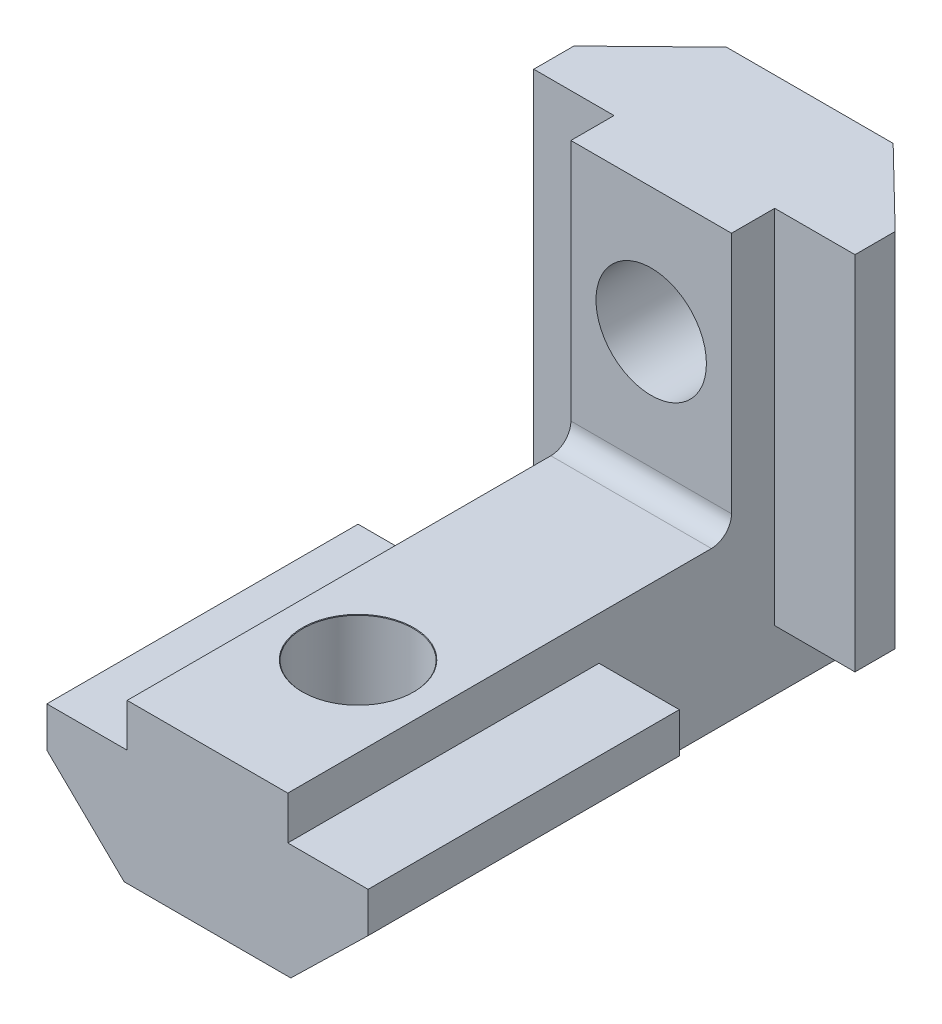
SolidWorks part; units mm, degrees
ref_plane "Piano frontale" through (0, 0, 0) normal (0, 0, 1) x (1, 0, 0)
ref_plane "Piano superiore" through (0, 0, 0) normal (0, 1, 0) x (1, 0, 0)
ref_plane "Piano destro" through (0, 0, 0) normal (1, 0, 0) x (0, 0, -1)
sketch "Schizzo1" plane through (0, 0, 0) normal (0, 0, 1) x (1, 0, 0)
  line L0 (-4.15, 0) -> (4.15, 0)
  line L1 (-4.15, 0) -> (-8, 3.75)
  line L2 (8, 5.75) -> (4, 5.75)
  line L3 (4, 5.75) -> (4, 7.9)
  line L4 (4, 7.9) -> (-4, 7.9)
  line L5 (-4, 7.9) -> (-4, 5.75)
  line L6 (-4, 5.75) -> (-8, 5.75)
  line L7 (-8, 3.75) -> (-8, 5.75)
  line L8 (0, 0) -> (0, 31.559) construction
  line L9 (4.15, 0) -> (8, 3.75)
  line L10 (8, 3.75) -> (8, 5.75)
  dimension "D1" = 8
  dimension "D2" = 8.3
  dimension "D3" = 16
  dimension "D4" = 7.9
  dimension "D5" = 5.75
  dimension "D6" = 2
extrude "Estrusione-Estrusione1" add sketch "Schizzo1" against normal blind 15.5
sketch "Schizzo2" plane through (0, 0, -15.5) normal (0, 0, -1) x (-1, 0, 0)
  line L0 (-4, 7.9) -> (-4, 0)
  line L1 (4.15, 0) -> (-4.15, 0) construction
  line L2 (-4, 0) -> (4, 0)
  line L3 (4, 0) -> (4, 7.9)
  line L4 (4, 7.9) -> (4, 5.75) construction
  line L5 (-4, 7.9) -> (4, 7.9) construction
  line L6 (4, 7.9) -> (-4, 7.9)
extrude "Estrusione-Estrusione2" add sketch "Schizzo2" along normal blind 14.5
ref_plane "Piano1" through (0, 21, 0) normal (0, -1, 0) x (-1, 0, 0)
sketch "Schizzo4" plane through (0, 21, 0) normal (0, -1, 0) x (-1, 0, 0)
  line L0 (-4.15, 30) -> (4.15, 30)
  line L1 (-4.15, 30) -> (-8, 26.25)
  line L2 (8, 24.25) -> (4, 24.25)
  line L3 (4, 24.25) -> (4, 22.1)
  line L4 (4, 22.1) -> (-4, 22.1)
  line L5 (-4, 22.1) -> (-4, 24.25)
  line L6 (-4, 24.25) -> (-8, 24.25)
  line L7 (8, 24.25) -> (8, 26.25)
  line L8 (4.15, 30) -> (8, 26.25)
  line L9 (-8, 24.25) -> (-8, 26.25)
  line L11 (4, 30) -> (-4, 30) construction
  line L12 (0, 30) -> (0, -0.5931) construction
  dimension "D1" = 8.3
  dimension "D2" = 8
  dimension "D3" = 7.9
  dimension "D4" = 2
  dimension "D5" = 16
  dimension "D6" = 5.75
extrude "Estrusione-Estrusione3" add sketch "Schizzo4" along normal offset from surface (18 mm away) 18 up to plane "Piano1"
fillet "Raccordo1" radius 1 1 edges at (0, 7.9, -22.1)
hole_wizard "Foro per Vite M5-1" positions "Schizzo6" profile "Schizzo7" hole size "M5" standard "Ansi Metric" end condition up to next
sketch "Schizzo6" plane through (0, 7.9, 0) normal (0, 1, 0) x (1, 0, 0)
  line L0 (0, 0) -> (0, 13.5128) construction
  line L1 (4, 0) -> (-4, 0) construction
  point P0 (0, 7.5)
  dimension "D1" = 7.5
sketch "Schizzo7" plane through (0, 7.9, -7.5) normal (1, 0, 0) x (0, 0, 1)
  line L0 (0, 0) -> (0, 7.9)
  line L1 (0, 7.9) -> (2.75, 7.9)
  line L2 (2.75, 7.9) -> (2.75, 0.025)
  line L3 (2.75, 0.025) -> (2.775, 0)
  line L5 (2.775, 0) -> (0, 0)
  line L6 (-2.75, 0.025) -> (-2.775, 0) construction
  line L11 (0, -6.35) -> (0, 107.95) construction
  dimension "Thru Hole Dia." = 5.5
  dimension "Thru Hole Depth" = 7.9
  dimension "Near C'Sink Dia." = 5.55
  dimension "Near C'Sink Angle" = 90
hole_wizard "Foro per Vite M5-2" positions "Schizzo9" profile "Schizzo10" hole size "M5" standard "ISO" end condition through all
sketch "Schizzo9" plane through (0, 0, -22.1) normal (0, 0, 1) x (1, 0, 0)
  line L0 (4, 21) -> (-4, 21) construction
  line L1 (0, 8.9) -> (0, 21) construction
  line L2 (-4, 8.9) -> (4, 8.9) construction
  line L4 (-4, 8.9) -> (-4, 21) construction
  line L5 (4, 8.9) -> (4, 21) construction
  point P0 (0, 14.75)
  dimension "D1" = 6.25
sketch "Schizzo10" plane through (0, 14.75, -22.1) normal (1, 0, 0) x (0, -1, 0)
  line L0 (0, 0) -> (0, 7.9)
  line L1 (0, 7.9) -> (2.75, 7.9)
  line L2 (2.75, 7.9) -> (2.75, 0)
  line L5 (2.75, 0) -> (0, 0)
  line L11 (0, -6.35) -> (0, 107.95) construction
  dimension "Thru Hole Dia." = 5.5
  dimension "Thru Hole Depth" = 7.9
